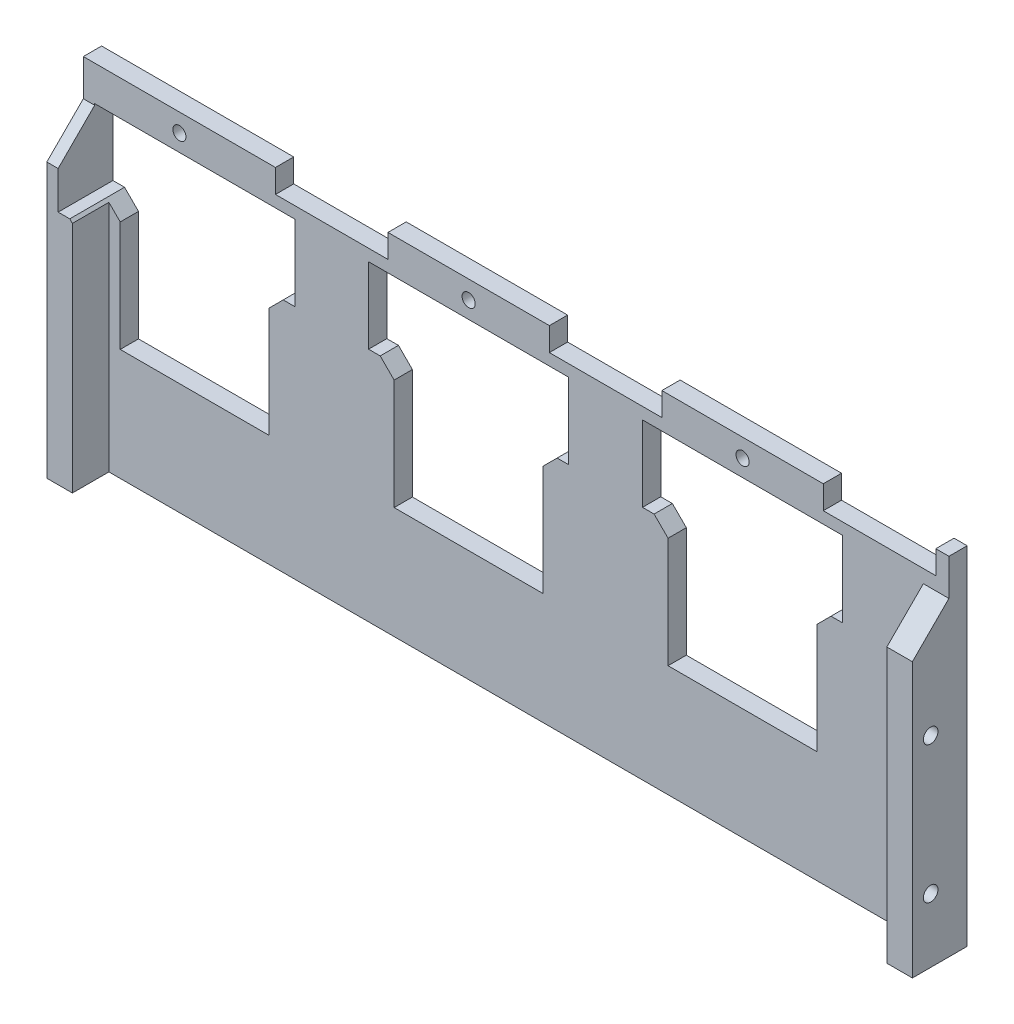
SolidWorks part; units mm, degrees
ref_plane "Płaszczyzna przednia" through (0, 0, 0) normal (0, 0, 1) x (1, 0, 0)
ref_plane "Płaszczyzna górna" through (0, 0, 0) normal (0, 1, 0) x (1, 0, 0)
ref_plane "Płaszczyzna prawa" through (0, 0, 0) normal (1, 0, 0) x (0, 0, -1)
sketch "Szkic1" plane through (0, 0, 0) normal (0, 0, 1) x (1, 0, 0)
  line L1 (-118.5, -72.5) -> (118.5, -72.5)
  line L2 (-118.5, -72.5) -> (-118.5, 72.5)
  line L3 (-118.5, 72.5) -> (118.5, 72.5)
  line L4 (118.5, -72.5) -> (118.5, 72.5)
  line L5 (0, 72.5) -> (0, -72.5) construction
  line L6 (-118.5, 0) -> (118.5, 0) construction
  point P0 (0, 0)
  dimension "D1" = 237
  dimension "D2" = 145
extrude "Dodanie-wyciągnięcie1" add sketch "Szkic1" along normal blind 5
sketch "Szkic2" plane through (0, 0, 5) normal (0, 0, 1) x (1, 0, 0)
  line L0 (118.5, -72.5) -> (118.5, 72.5) construction
  line L1 (118.5, 62.5) -> (111.5, 62.5)
  line L2 (118.5, 62.5) -> (118.5, -72.5)
  line L3 (118.5, -72.5) -> (111.5, -72.5)
  line L4 (111.5, 62.5) -> (111.5, -72.5)
  line L5 (115, -72.5) -> (115, 62.5) construction
  line L6 (118.5, -5) -> (111.5, -5) construction
  line L7 (118.5, 72.5) -> (-118.5, 72.5) construction
  line L9 (0, 0) -> (0, 72.5) construction
  line L10 (-118.5, -5) -> (-111.5, -5) construction
  line L11 (-115, -72.5) -> (-115, 62.5) construction
  line L12 (-111.5, 62.5) -> (-111.5, -72.5)
  line L13 (-118.5, -72.5) -> (-111.5, -72.5)
  line L14 (-118.5, 62.5) -> (-118.5, -72.5)
  line L15 (-118.5, 62.5) -> (-111.5, 62.5)
  line L16 (-118.5, -72.5) -> (118.5, -72.5) construction
  point P20 (-115, -5)
  point P300 (115, -5)
  dimension "D1" = 10
  dimension "D3" = 7
extrude "Dodanie-wyciągnięcie2" add sketch "Szkic2" along normal blind 10
sketch "Szkic3" plane through (118.5, 0, 0) normal (1, 0, 0) x (0, 0, -1)
  line L0 (-10, 62.5) -> (-10, -72.5) construction
  line L1 (-15, 62.5) -> (-5, 62.5) construction
  line L3 (0, -5) -> (-15, -5) construction
  line L5 (-15, -72.5) -> (-15, 62.5) construction
  line L6 (-15, -72.5) -> (-15, 62.5) construction
  line L7 (0, -72.5) -> (0, 72.5) construction
  line L8 (-15, -72.5) -> (0, -72.5) construction
  point P6 (-10, 32.5)
  point P7 (-10, -5)
  point P8 (-10, -42.5)
  dimension "D1" = 37.5
hole_wizard "Otwór Ø4.0 (4)1" positions "Szkic3" profile "Szkic4" hole size "Ø4.0" standard "DIN"
sketch "Szkic4" plane through (118.5, -42.5, 10) normal (0, 1, 0) x (0, 0, -1)
  line L0 (0, 0) -> (0, 6.7)
  line L1 (0, 6.7) -> (2, 6.7)
  line L2 (2, 6.7) -> (2, 0)
  line L5 (2, 0) -> (0, 0)
  line L10 (0, 6.7) -> (-2, 6.7) construction
  line L11 (0, -6.35) -> (0, 107.95) construction
  dimension "Średnica otworu" = 4
  dimension "Głębokość otworu" = 6.7
  dimension "Kąt wiertła" = 180
ref_plane "Płaszczyzna1" through (0, 0, 0) normal (-1, 0, 0) x (0, 0, 1)
mirror "Lustro1" about plane through (0, 0, 0) normal (-1, 0, 0) of "Otwór Ø4.0 (4)1"
chamfer "Sfazowanie1" distance 10 angle 45 2 edges at (-115, 62.5, 15) (115, 62.5, 15)
sketch "Szkic5" plane through (0, 0, 0) normal (0, 0, -1) x (-1, 0, 0)
  line L1 (-86, 42.5546) -> (-86, 42.5)
  line L2 (-84.5, 72.5) -> (-114.5, 72.5)
  line L4 (-11, 42.5546) -> (-11, 42.5)
  line L6 (-9.5, 72.5) -> (-39.5, 72.5)
  line L7 (64, 42.5546) -> (64, 42.5)
  line L15 (-86.2203, 42.1546) -> (-85.2828, 41.2172)
  line L16 (-85.2828, 41.2172) -> (-82.4, 38.3343)
  line L17 (-82.4, 38.3343) -> (-82.4, 8.1)
  line L22 (-82.4, 8.1) -> (-41.6, 8.1)
  line L39 (-41.6, 8.1) -> (-41.6, 38.3343)
  line L44 (-41.6, 38.3343) -> (-38.7172, 41.2172)
  line L48 (-38.7172, 41.2172) -> (-37.7797, 42.1546)
  line L86 (-37.7797, 42.1546) -> (-34.6, 42.1546)
  line L88 (-34.6, 42.1546) -> (-34.6, 62.9)
  line L90 (-34.6, 62.9) -> (-89.4, 62.9)
  line L94 (-89.4, 62.9) -> (-89.4, 42.1546)
  line L102 (-89.4, 42.1546) -> (-86.2203, 42.1546)
  line L103 (-84.1, 72.9) -> (-114.9, 72.9)
  line L110 (-114.9, 72.9) -> (-114.9, 66.1)
  line L115 (-114.9, 66.1) -> (-84.1, 66.1)
  line L121 (-84.1, 66.1) -> (-84.1, 72.9)
  line L127 (-11.2203, 42.1546) -> (-10.2828, 41.2172)
  line L128 (-10.2828, 41.2172) -> (-7.4, 38.3343)
  line L129 (-7.4, 38.3343) -> (-7.4, 8.1)
  line L132 (-7.4, 8.1) -> (33.4, 8.1)
  line L134 (33.4, 8.1) -> (33.4, 38.3343)
  line L135 (33.4, 38.3343) -> (36.2828, 41.2172)
  line L168 (36.2828, 41.2172) -> (37.2203, 42.1546)
  line L183 (37.2203, 42.1546) -> (40.4, 42.1546)
  line L200 (40.4, 42.1546) -> (40.4, 62.9)
  line L201 (40.4, 62.9) -> (-14.4, 62.9)
  line L206 (-14.4, 62.9) -> (-14.4, 42.1546)
  line L207 (-14.4, 42.1546) -> (-11.2203, 42.1546)
  line L208 (-9.1, 72.9) -> (-39.9, 72.9)
  line L209 (-39.9, 72.9) -> (-39.9, 66.1)
  line L210 (-39.9, 66.1) -> (-9.1, 66.1)
  line L215 (-9.1, 66.1) -> (-9.1, 72.9)
  line L216 (36, 41.5) -> (37, 42.5) construction
  line L225 (37, 42.5) -> (37, 48.5) construction
  line L277 (33, 38.5) -> (36, 41.5) construction
  line L278 (63.7797, 42.1546) -> (64.7172, 41.2172)
  line L288 (64.7172, 41.2172) -> (67.6, 38.3343)
  line L289 (67.6, 38.3343) -> (67.6, 8.1)
  line L290 (67.6, 8.1) -> (108.4, 8.1)
  line L292 (108.4, 8.1) -> (108.4, 38.3343)
  line L293 (108.4, 38.3343) -> (111.2828, 41.2172)
  line L294 (111.2828, 41.2172) -> (112.2203, 42.1546)
  line L311 (-11, 42.5) -> (-10, 41.5) construction
  line L314 (112.2203, 42.1546) -> (115.4, 42.1546)
  line L318 (115.4, 42.1546) -> (115.4, 62.9)
  line L320 (-10, 41.5) -> (-7, 38.5) construction
  line L333 (115.4, 62.9) -> (60.6, 62.9)
  line L334 (60.6, 62.9) -> (60.6, 42.1546)
  line L335 (60.6, 42.1546) -> (63.7797, 42.1546)
  line L336 (35.1, 72.9) -> (35.1, 66.1)
  line L337 (35.1, 66.1) -> (65.9, 66.1)
  line L338 (65.9, 66.1) -> (65.9, 72.9)
  line L340 (65.9, 72.9) -> (35.1, 72.9)
  line L349 (-7, 38.5) -> (-7, 8.5) construction
  line L350 (-7, 8.5) -> (33, 8.5) construction
  line L351 (33, 8.5) -> (33, 38.5) construction
  line L407 (111, 41.5) -> (112, 42.5)
  line L408 (112, 42.5) -> (112, 42.5546)
  line L410 (108, 38.5) -> (111, 41.5)
  line L412 (61, 62.5) -> (61, 42.5546)
  line L413 (61, 42.5546) -> (64, 42.5546)
  line L421 (112, 42.5546) -> (115, 42.5546)
  line L422 (115, 42.5546) -> (115, 62.5)
  line L423 (115, 62.5) -> (61, 62.5)
  line L424 (64, 42.5) -> (65, 41.5)
  line L428 (65, 41.5) -> (68, 38.5)
  line L445 (68, 38.5) -> (68, 8.5)
  line L446 (68, 8.5) -> (108, 8.5)
  line L447 (108, 8.5) -> (108, 38.5)
  line L449 (36, 41.5) -> (37, 42.5)
  line L450 (37, 42.5) -> (37, 42.5546)
  line L452 (33, 38.5) -> (36, 41.5)
  line L454 (-14, 62.5) -> (-14, 42.5546)
  line L455 (-14, 42.5546) -> (-11, 42.5546)
  line L463 (37, 42.5546) -> (40, 42.5546)
  line L464 (40, 42.5546) -> (40, 62.5)
  line L465 (40, 62.5) -> (-14, 62.5)
  line L466 (-11, 42.5) -> (-10, 41.5)
  line L470 (-10, 41.5) -> (-7, 38.5)
  line L487 (-7, 38.5) -> (-7, 8.5)
  line L488 (-7, 8.5) -> (33, 8.5)
  line L489 (33, 8.5) -> (33, 38.5)
  line L490 (-42, 38.5) -> (-39, 41.5)
  line L493 (-39, 41.5) -> (-38, 42.5)
  line L494 (-38, 42.5) -> (-38, 42.5546)
  line L496 (-86, 42.5) -> (-85, 41.5)
  line L500 (-85, 41.5) -> (-82, 38.5)
  line L502 (-89, 62.5) -> (-89, 42.5546)
  line L503 (-89, 42.5546) -> (-86, 42.5546)
  line L511 (-38, 42.5546) -> (-35, 42.5546)
  line L512 (-35, 42.5546) -> (-35, 62.5)
  line L513 (-35, 62.5) -> (-89, 62.5)
  line L529 (-82, 38.5) -> (-82, 8.5)
  line L530 (-82, 8.5) -> (-42, 8.5)
  line L531 (-42, 8.5) -> (-42, 38.5)
  line L533 (35.5, 72.5) -> (35.5, 66.5)
  line L534 (35.5, 66.5) -> (65.5, 66.5)
  line L535 (65.5, 66.5) -> (65.5, 72.5)
  line L537 (-39.5, 72.5) -> (-39.5, 66.5)
  line L538 (-39.5, 66.5) -> (-9.5, 66.5)
  line L539 (-9.5, 66.5) -> (-9.5, 72.5)
  line L540 (-114.5, 72.5) -> (-114.5, 66.5)
  line L541 (-114.5, 66.5) -> (-84.5, 66.5)
  line L542 (-84.5, 66.5) -> (-84.5, 72.5)
  line L548 (-118.5, 72.5) -> (-118.5, -72.5)
  line L549 (-118.5, -72.5) -> (118.5, -72.5)
  line L550 (118.5, -72.5) -> (118.5, 72.5)
  line L551 (118.5, 72.5) -> (-118.5, 72.5)
  line L555 (65.5, 72.5) -> (35.5, 72.5)
  line M8 (118.5, 72.5) -> (-118.5, 72.5)
  dimension "D1" = 0
extrude "Wytnij-wyciągnięcie1" cut sketch "Szkic5" against normal up to next contours L530 L531 L490 L493 L494 L511 L512 L513 L502 L503 L1 L496 L500 L529 | L541 L542 L540 M8 | L542 L541 L540 L110 L115 L121 M8 | L94 L102 L15 L16 L17 L22 L39 L44 L48 L86 L88 L90 L531 L530 L529 L500 L496 L1 L503 L502 L513 L512 L511 L494 L493 L490 | L488 L489 L452 L449 L450 L463 L464 L465 L454 L455 L4 L466 L470 L487 | L206 L207 L127 L128 L129 L132 L134 L135 L168 L183 L200 L201 L489 L488 L487 L470 L466 L4 L455 L454 L465 L464 L463 L450 L449 L452 | L538 L539 L537 M8 | L539 L538 L537 L209 L210 L215 M8 | L446 L447 L410 L407 L408 L421 L422 L423 L412 L413 L7 L424 L428 L445 | L334 L335 L278 L288 L289 L290 L292 L293 L294 L314 L318 L333 L447 L446 L445 L428 L424 L7 L413 L412 L423 L422 L421 L408 L407 L410 | L534 L535 L533 M8 | L535 L534 L533 L336 L337 L338 M8 region at (62, 37.4744, 0) region at (99.5, 69.5, 0) region at (84.3, 72.1854, 0) region at (39.7, 72.1854, 0) region at (24.5, 69.5, 0) region at (-35.3, 72.1854, 0) region at (-50.5, 69.5, 0) region at (-13, 37.4744, 0) region at (-88, 37.4744, 0) region at (87.8102, 42.2321, 0) region at (12.8102, 42.2321, 0) region at (-62.1898, 42.2321, 0)
ref_plane "Płaszczyzna2" through (0, -22.5, 0) normal (0, -1, 0) x (-1, 0, 0)
split "Podziel1" trim tools "Płaszczyzna2" bodies to split 113 resulting bodies 107 108
sketch "Szkic6" plane through (0, 0, 0) normal (0, 0, -1) x (-1, 0, 0)
  line L3 (-62, 72.5) -> (-62, 67.5) construction
  line L4 (-84.1, 72.5) -> (-39.9, 72.5) construction
  line L6 (13, 72.5) -> (13, 67.5) construction
  line L7 (-9.1, 72.5) -> (35.1, 72.5) construction
  line L9 (92.2, 72.5) -> (92.2, 67.5) construction
  line L10 (65.9, 72.5) -> (118.5, 72.5) construction
  point P18 (-62, 67.5)
  point P20 (13, 67.5)
  point P22 (92.2, 67.5)
  dimension "D1" = 5
hole_wizard "Pogłębienie walcowe pod M3 Śrubę z łbem stożkowym ściętym1" positions "Szkic6" profile "Szkic7" counterbore size "M3" standard "DIN"
sketch "Szkic7" plane through (62, 67.5, 0) normal (1, 0, 0) x (0, 1, 0)
  line L0 (0, 0) -> (0, 7.7815)
  line L1 (0, 7.7815) -> (1.8, 6.7)
  line L2 (1.8, 6.7) -> (1.8, 2.4)
  line L3 (1.8, 2.4) -> (3.5, 2.4)
  line L4 (3.5, 2.4) -> (3.5, 0)
  line L5 (3.5, 0) -> (0, 0)
  line L10 (0, 7.7815) -> (-1.8, 6.7) construction
  line L11 (0, -6.35) -> (0, 107.95) construction
  dimension "Średnica otworu" = 3.6
  dimension "Głębokość otworu" = 6.7
  dimension "Średnica pogłębienia walcowego" = 7
  dimension "Głębokość pogłębienia walcowego" = 2.4
  dimension "Kąt wiertła" = 118
delete or keep bodies "Obiekt-Usuń/zachowaj 1" type delete bodies bodies 108
